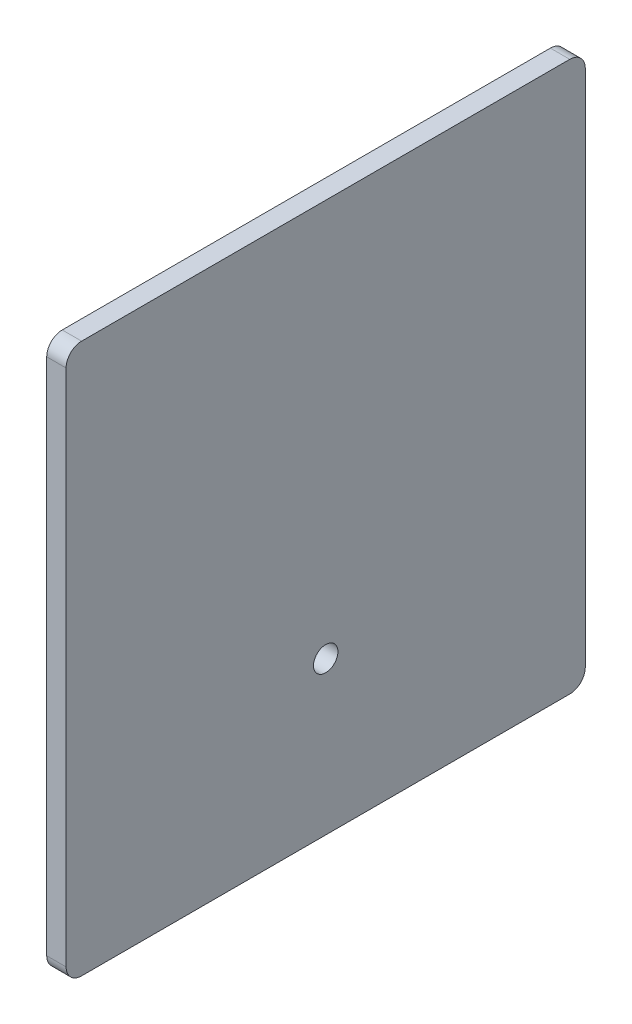
SolidWorks part; units mm, degrees
material "Acrylic (Medium-high impact)"
ref_plane "Front Plane" through (0, 0, 0) normal (0, 0, 1) x (1, 0, 0)
ref_plane "Top Plane" through (0, 0, 0) normal (0, 1, 0) x (1, 0, 0)
ref_plane "Right Plane" through (0, 0, 0) normal (1, 0, 0) x (0, 0, -1)
sketch "Sketch1" plane through (0, 0, 0) normal (1, 0, 0) x (0, 0, -1)
  line L1 (42.5, -45) -> (-42.5, -45)
  line L2 (42.5, -45) -> (42.5, 45)
  line L3 (42.5, 45) -> (-42.5, 45)
  line L4 (-42.5, -45) -> (-42.5, 45)
  line L5 (42.5, -45) -> (-42.5, 45) construction
  line L6 (42.5, 45) -> (-42.5, -45) construction
  point P0 (0, 0)
  dimension "D1" = 85
  dimension "D2" = 90
extrude "Boss-Extrude1" add sketch "Sketch1" along normal blind 3.175
sketch "Sketch2" plane through (3.175, 0, 0) normal (1, 0, 0) x (0, 0, -1)
  line L0 (-42.5, 45) -> (-42.5, -45) construction
  line L1 (-42.5, -45) -> (42.5, -45) construction
  circle A0 centre (0, -20) radius 2
  dimension "D3" = 4
  dimension "D1" = 42.5
  dimension "D2" = 25
extrude "Cut-Extrude1" cut sketch "Sketch2" against normal through all
fillet "Fillet1" radius 2.54 4 edges at (1.5875, -45, 42.5) (1.5875, -45, -42.5) (1.5875, 45, -42.5) (1.5875, 45, 42.5)
